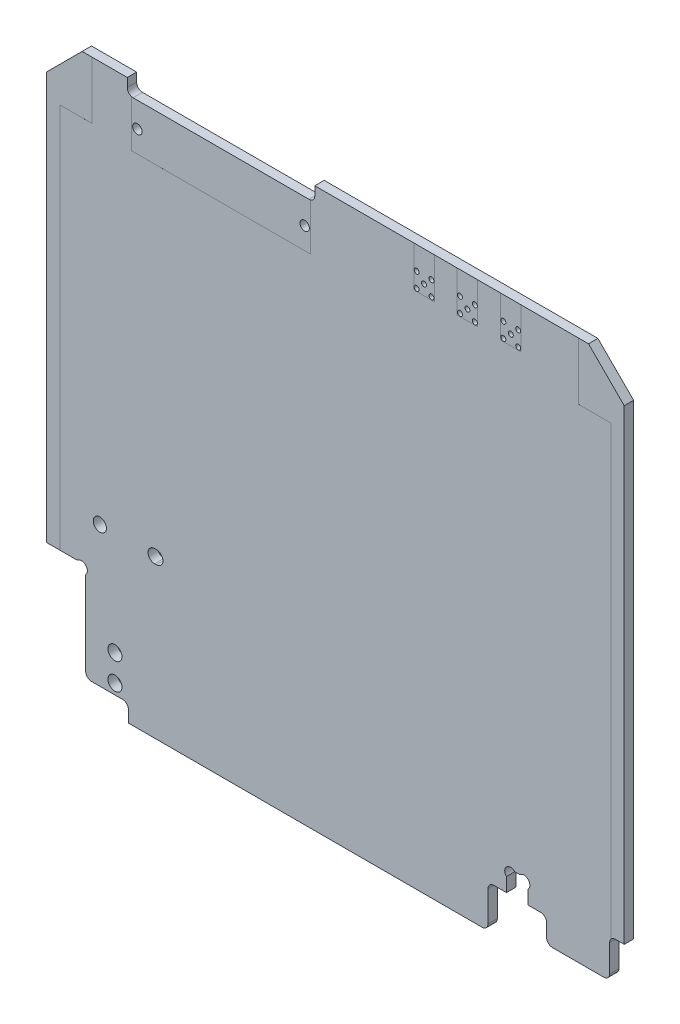
SolidWorks part; units mm, degrees
material "Oshpark board"
ref_plane "Front Plane" through (0, 0, 0) normal (0, 0, 1) x (1, 0, 0)
ref_plane "Top Plane" through (0, 0, 0) normal (0, 1, 0) x (1, 0, 0)
ref_plane "Right Plane" through (0, 0, 0) normal (1, 0, 0) x (0, 0, -1)
ref_plane "Plane4" through (0, 0, -0.0125) normal (0, 0, -1) x (-1, 0, 0)
sketch "Sketch1" plane through (0, 0, -0.0125) normal (0, 0, -1) x (-1, 0, 0)
  line L0 (35.3, -50) -> (35.3, -48)
  line L1 (36.3, -47) -> (45.8, -47)
  line L2 (46.8, -46) -> (46.8, -41.4)
  line L3 (47.8, -40.4) -> (49.3, -40.4)
  line L4 (49.3, -40.4) -> (49.3, 39.2)
  line L5 (49.3, 39.2) -> (43.2, 45.3)
  line L6 (43.2, 45.3) -> (35.5, 45.3)
  line L7 (35.5, 45.3) -> (35.5, 43.8)
  line L8 (34.5, 42.8) -> (4.5, 42.8)
  line L9 (3.5, 43.8) -> (3.5, 45.3)
  line L10 (3.5, 45.3) -> (-43.2, 45.3)
  line L11 (-43.2, 45.3) -> (-49.3, 39.2)
  line L12 (-49.3, 39.2) -> (-49.3, -40.4)
  line L13 (-49.3, -40.4) -> (-47.8, -40.4)
  line L14 (-46.8, -41.4) -> (-46.8, -46)
  line L15 (-45.8, -47) -> (-36.3, -47)
  line L16 (-35.3, -48) -> (-35.3, -50)
  line L17 (-35.3, -50) -> (35.3, -50)
  line L18 (0, -50) -> (0, 45.3) construction
  line L19 (19.5, 42.8) -> (19.5, 25.5258) construction
  line L20 (-13.87, 41.37) -> (-16.41, 38.83) construction
  line L21 (-21.27, 41.37) -> (-23.81, 38.83) construction
  line L22 (-28.67, 41.37) -> (-31.21, 38.83) construction
  arc A0 (35.3, -48) -> (36.3, -47) centre (36.3, -48) cw
  arc A1 (45.8, -47) -> (46.8, -46) centre (45.8, -46) ccw
  arc A2 (46.8, -41.4) -> (47.8, -40.4) centre (47.8, -41.4) cw
  arc A3 (35.5, 43.8) -> (34.5, 42.8) centre (34.5, 43.8) cw
  arc A4 (4.5, 42.8) -> (3.5, 43.8) centre (4.5, 43.8) cw
  arc A5 (-47.8, -40.4) -> (-46.8, -41.4) centre (-47.8, -41.4) cw
  arc A6 (-46.8, -46) -> (-45.8, -47) centre (-45.8, -46) ccw
  arc A7 (-36.3, -47) -> (-35.3, -48) centre (-36.3, -48) cw
  circle A8 centre (-21.27, 41.37) radius 0.425
  circle A9 centre (-23.81, 41.37) radius 0.425
  circle A10 centre (-22.54, 40.1) radius 0.425
  circle A11 centre (-13.87, 41.37) radius 0.425
  circle A12 centre (-23.81, 38.83) radius 0.425
  circle A13 centre (-16.41, 41.37) radius 0.425
  circle A14 centre (-15.14, 40.1) radius 0.425
  circle A15 centre (-21.27, 38.83) radius 0.425
  circle A16 centre (-28.67, 41.37) radius 0.425
  circle A17 centre (-31.21, 41.37) radius 0.425
  circle A18 centre (-16.41, 38.83) radius 0.425
  circle A19 centre (-29.94, 40.1) radius 0.425
  circle A20 centre (-31.21, 38.83) radius 0.425
  circle A21 centre (-28.67, 38.83) radius 0.425
  circle A22 centre (33.775, 38.54) radius 0.8
  circle A23 centre (5.225, 38.54) radius 0.8
  circle A24 centre (-13.87, 38.83) radius 0.425
  point P35 (-15.14, 40.1)
  dimension "D7" = 2.5
  dimension "D8" = 1.6
  dimension "D9" = 14.275
  dimension "D10" = 4.26
  dimension "D11" = 1
  dimension "D12" = 1
  dimension "D13" = 1
  dimension "D14" = 1
  dimension "D15" = 1
  dimension "D16" = 1
  dimension "D17" = 1
  dimension "D18" = 1
  dimension "D26" = 0.85
  dimension "D1" = 98.6
  dimension "D2" = 95.3
  dimension "D3" = 14
  dimension "D4" = 9.6
  dimension "D5" = 2.5
  dimension "D6" = 3
  dimension "D19" = 14
  dimension "D20" = 2.5
  dimension "D21" = 6.1
  dimension "D22" = 6.1
  dimension "D23" = 32
  dimension "D24" = 2.54
  dimension "D25" = 2.54
  dimension "D28" = 7.4
  dimension "D29" = 3.93
  dimension "D30" = 35.43
  dimension "D31" = 45
  dimension "D32" = 45
  dimension "D33" = 29.8
  dimension "D34" = 50
  dimension "D27" = 3
extrude "Boss-Extrude1" add sketch "Sketch1" against normal blind 1.6
sketch "thermalContacts_lower" plane through (0, 0, -0.0125) normal (0, 0, -1) x (-1, 0, 0)
  line L3 (47, 35.5) -> (47, -41.5)
  line L4 (41.5, 35.5) -> (41.5, 41.5)
  line L5 (41.5, 35.5) -> (47, 35.5)
  line L9 (-47, 35.5) -> (-47, -41.5)
  line L10 (-41.5, 35.5) -> (-47, 35.5)
  line L11 (-41.5, 35.5) -> (-41.5, 41.5)
  line L14 (-41.5, 41.5) -> (-41.5, 47)
  line L15 (-41.5, 41.5) -> (-49.5, 41.5) construction
  line L18 (41.5, 41.5) -> (41.5, 48.7577)
  line L19 (41.5, 41.5) -> (49.5, 41.5) construction
  line L20 (47, -41.5) -> (59.8273, -41.5)
  line L21 (59.8273, -41.5) -> (59.8273, 48.7577)
  line L22 (-56.1922, 47) -> (-41.5, 47)
  line L23 (41.5, 48.7577) -> (59.8273, 48.7577)
  line L24 (-56.1922, 47) -> (-56.1922, -41.5)
  line L25 (-47, -41.5) -> (-56.1922, -41.5)
  line L26 (43.2, 45.3) -> (35.5, 45.3) construction
  line L27 (49.3, -40.4) -> (49.3, 39.2) construction
  line L28 (-35.3, -50) -> (35.3, -50) construction
  line L29 (-49.3, 39.2) -> (-49.3, -40.4) construction
  line L30 (3.5, 45.3) -> (-43.2, 45.3) construction
  point P26 (44.0756, 48.2853)
  dimension "D1" = 9.8
  dimension "D2" = 7.8
  dimension "D3" = 2.3
  dimension "D4" = 8.5
  dimension "D5" = 8.5
  dimension "D6" = 2.3
  dimension "D7" = 7.8
  dimension "D8" = 9.8
sketch "thermalContacts_upper" plane through (0, 0, 1.5875) normal (0, 0, 1) x (1, 0, 0)
  line L3 (-47, 35.5) -> (-47, -41.5)
  line L4 (-41.5, 35.5) -> (-41.5, 41.5)
  line L5 (-41.5, 35.5) -> (-47, 35.5)
  line L9 (47, 35.5) -> (47, -41.5)
  line L10 (41.5, 35.5) -> (47, 35.5)
  line L11 (41.5, 35.5) -> (41.5, 41.5)
  line L14 (41.5, 41.5) -> (41.5, 47)
  line L15 (41.5, 41.5) -> (49.5, 41.5) construction
  line L18 (-41.5, 41.5) -> (-41.5, 47)
  line L19 (-41.5, 41.5) -> (-49.5, 41.5) construction
  line L20 (47, -41.5) -> (59.8273, -41.5)
  line L21 (59.8273, -41.5) -> (59.8273, 47)
  line L22 (59.8273, 47) -> (41.5, 47)
  line L23 (-41.5, 47) -> (-56.1922, 47)
  line L24 (-56.1922, 47) -> (-56.1922, -41.5)
  line L25 (-56.1922, -41.5) -> (-47, -41.5)
extrude "Cut-Extrude1" cut sketch "thermalContacts_lower" against normal blind 0.0001
extrude "Cut-Extrude2" cut sketch "thermalContacts_upper" against normal blind 0.0001
sketch "partFootprints" plane through (0, 0, 1.5875) normal (0, 0, 1) x (1, 0, 0)
  line L0 (-34.74, 34.84) -> (-34.74, 42.8292)
  line L1 (-4.26, 34.84) -> (-34.74, 34.84)
  line L2 (-41.5, 45.3) -> (-35.5, 45.3) construction
  line L3 (-36.1132, 45.3) -> (-39.5054, 45.3) construction
  line L4 (-4.26, 34.84) -> (-4.26, 42.8292)
  line L5 (-49.3, -40.4) -> (-49.3, 39.2) construction
  line L6 (13.39, 45.3) -> (13.39, 38.35)
  line L7 (13.39, 38.35) -> (16.89, 38.35)
  line L8 (16.89, 38.35) -> (16.89, 45.3)
  line L9 (16.89, 45.3) -> (13.39, 45.3)
  line L10 (20.79, 45.3) -> (20.79, 38.35)
  line L11 (20.79, 38.35) -> (24.29, 38.35)
  line L12 (24.29, 38.35) -> (24.29, 45.3)
  line L13 (24.29, 45.3) -> (20.79, 45.3)
  line L14 (28.19, 45.3) -> (28.19, 38.35)
  line L15 (28.19, 38.35) -> (31.69, 38.35)
  line L16 (31.69, 38.35) -> (31.69, 45.3)
  line L17 (31.69, 45.3) -> (28.19, 45.3)
  line L19 (14.12, 38.35) -> (16.16, 38.35) construction
  line L20 (-34.74, 42.8292) -> (-4.26, 42.8292)
  line L21 (-3.5, 45.3) -> (41.5, 45.3) construction
  line L22 (14.12, 38.35) -> (16.16, 38.35) construction
  line L23 (13.39, 41.85) -> (13.39, 38.35) construction
  line L24 (16.89, 41.85) -> (16.89, 38.35) construction
  line L25 (13.39, 41.85) -> (13.39, 38.35) construction
  line L26 (16.89, 41.85) -> (16.89, 38.35) construction
  arc A0 (-35.5, 43.8) -> (-34.5, 42.8) centre (-34.5, 43.8) ccw construction
  arc A1 (-4.5, 42.8) -> (-3.5, 43.8) centre (-4.5, 43.8) ccw construction
  dimension "D1" = 10.46
  dimension "D2" = 14.56
  dimension "D3" = 30.48
  dimension "D7" = 7.4
  dimension "D6" = 3
extrude "Cut-Extrude3" cut sketch "partFootprints" against normal blind 0.0001
sketch "Sketch2" plane through (0, 0, 1.5875) normal (0, 0, 1) x (1, 0, 0)
  line L0 (35.1, -50) -> (35.1, -37.5518) construction
  line L1 (35.3, -50) -> (-35.3, -50) construction
  line L2 (27, -50) -> (27, -36.9095) construction
  line L3 (35.3, -48) -> (35.3, -50) construction
  line L4 (29.2, -42.8) -> (29.2, -40.4142)
  line L5 (27, -39) -> (35.1, -39) construction
  line L6 (30.6142, -39) -> (31.4858, -39)
  line L7 (32.9, -40.4142) -> (32.9, -42.8)
  line L8 (26.05, -50) -> (36.05, -50)
  line L9 (30.6142, -39) -> (31.4858, -39) construction
  line L10 (26.05, -50) -> (26.05, -42.8)
  line L11 (26.05, -42.8) -> (29.2, -42.8)
  line L12 (31.05, -39) -> (31.05, -50) construction
  line L13 (36.05, -42.8) -> (32.9, -42.8)
  line L14 (36.05, -50) -> (36.05, -42.8)
  line L15 (48.0683, 27.2) -> (36.7758, 27.2) construction
  line L16 (48.0683, 35.5) -> (35.6387, 35.5) construction
  line L17 (42.1, 29.55) -> (39.0071, 29.55) construction
  line L18 (38.3, 35.5) -> (38.3, 27.2) construction
  line L19 (38.3, 30.2571) -> (38.3, 32.4429) construction
  line L20 (39.0071, 33.15) -> (42.1, 33.15) construction
  line L21 (49.3, 29.1) -> (49.3, 33.6) construction
  line L22 (38.3, 30.2571) -> (38.3, 32.4429) construction
  line L23 (49.3, 29.1) -> (42.1, 29.1) construction
  line L24 (42.1, 29.1) -> (42.1, 29.55) construction
  line L25 (38.3, 31.35) -> (49.3, 31.35) construction
  line L26 (42.1, 33.6) -> (42.1, 33.15) construction
  line L27 (49.3, 33.6) -> (42.1, 33.6) construction
  line L28 (49.3, -40.4) -> (49.3, 39.2) construction
  line L30 (31.69, 45.3) -> (41.5, 45.3) construction
  arc A0 (29.2, -40.4142) -> (30.6142, -39) centre (29.9071, -39.7071) cw
  arc A1 (31.4858, -39) -> (32.9, -40.4142) centre (32.1929, -39.7071) cw
  arc A2 (39.0071, 29.55) -> (38.3, 30.2571) centre (38.6536, 29.9036) cw construction
  arc A3 (38.3, 32.4429) -> (39.0071, 33.15) centre (38.6536, 32.7964) cw construction
  point P8 (35.3, -49)
  point P39 (38.3, 31.35)
  point P46 (38.3, 31.35)
  point P47 (38.3, 29.55)
  point P48 (38.3, 33.15)
  point P57 (31.05, -39)
  point P59 (32.9, -39)
  point P60 (29.2, -39)
  dimension "D5" = 1
  dimension "D8" = 0.5
  dimension "D1" = 0.2
  dimension "D2" = 8.3
  dimension "D3" = 3.7
  dimension "D4" = 11
  dimension "D6" = 3.8
  dimension "D7" = 10
  dimension "D9" = 3.6
  dimension "D10" = 11
  dimension "D11" = 3.8
  dimension "D12" = 4.5
  dimension "D13" = 9.8
  dimension "D14" = 8.3
extrude "Cut-Extrude4" cut sketch "Sketch2" against normal through all
sketch "Sketch3" plane through (0, 0, 1.5875) normal (0, 0, 1) x (1, 0, 0)
  line L0 (45.8, -47) -> (36.3, -47) construction
  line L1 (31.741, -47) -> (39.5208, -47)
  line L2 (31.741, -47) -> (31.741, -52.1552)
  line L3 (31.741, -52.1552) -> (39.5208, -52.1552)
  line L4 (39.5208, -47) -> (39.5208, -52.1552)
extrude "Cut-Extrude5" cut sketch "Sketch3" against normal blind 10
fillet "Fillet1" radius 1 4 edges at (36.05, -42.8, 0.7875) (26.05, -42.8, 0.7875) (36.05, -47, 0.7875) (26.05, -50, 0.7875)
sketch "Sketch4" plane through (0, 0, 1.5875) normal (0, 0, 1) x (1, 0, 0)
  line L0 (-36.3, -47) -> (-45.8, -47) construction
  line L1 (-51.3808, -30.3) -> (-44.0142, -30.3)
  line L2 (-51.3808, -30.3) -> (-51.3808, -47)
  line L3 (-51.3808, -47) -> (-42.6, -47)
  line L4 (-42.6, -31.7142) -> (-42.6, -47)
  line L5 (-42.8, -37.156) -> (-42.8, -48.7489) construction
  line L6 (-44.0142, -30.3) -> (-42.6, -30.3) construction
  line L7 (-42.6, -30.3) -> (-42.6, -31.7142) construction
  arc A0 (-44.0142, -30.3) -> (-42.6, -31.7142) centre (-43.3071, -31.0071) cw
  point P11 (-42.6, -30.3)
  dimension "D1" = 1
  dimension "D2" = 0.2
  dimension "D3" = 16.7
extrude "Cut-Extrude6" cut sketch "Sketch4" against normal through all
fillet "Fillet2" radius 1 1 edges at (-42.6, -47, 0.7875)
sketch "Sketch5" plane through (0, 0, 1.5875) normal (0, 0, 1) x (1, 0, 0)
  line L1 (-30.525, -24.225) -> (-30.825, -24.225)
  line L3 (-30.825, -21.975) -> (-30.525, -21.975)
  line L4 (-49.3, -30.3) -> (-49.3, 39.2) construction
  line L5 (-36.3, -47) -> (-41.6, -47) construction
  circle A1 centre (-40.175, -23.1) radius 1.125
  arc A4 (-30.825, -21.975) -> (-30.825, -24.225) centre (-30.825, -23.1) ccw
  arc A5 (-30.525, -24.225) -> (-30.525, -21.975) centre (-30.525, -23.1) ccw
  point P12 (0, 0)
  point P13 (0, 0)
  point P14 (-30.825, -21.975)
  point P15 (-30.525, -24.225)
  point P16 (-30.525, -24.225)
  dimension "D1" = 2.25
  dimension "D4" = 1.125
  dimension "D2" = 9.125
  dimension "D3" = 23.9
  dimension "D5" = 0.3
  dimension "D6" = 18.475
extrude "Cut-Extrude7" cut sketch "Sketch5" against normal through all
sketch "Sketch6" plane through (0, 0, 1.5875) normal (0, 0, 1) x (1, 0, 0)
  circle A1 centre (-37.6, -40.75) radius 1.2
  circle A2 centre (-37.6, -45.25) radius 1.2 construction
  circle A3 centre (-37.6, -45.25) radius 1.2
  circle A4 centre (-37.6, -40.75) radius 1.2 construction
extrude "Cut-Extrude8" cut sketch "Sketch6" against normal through all
